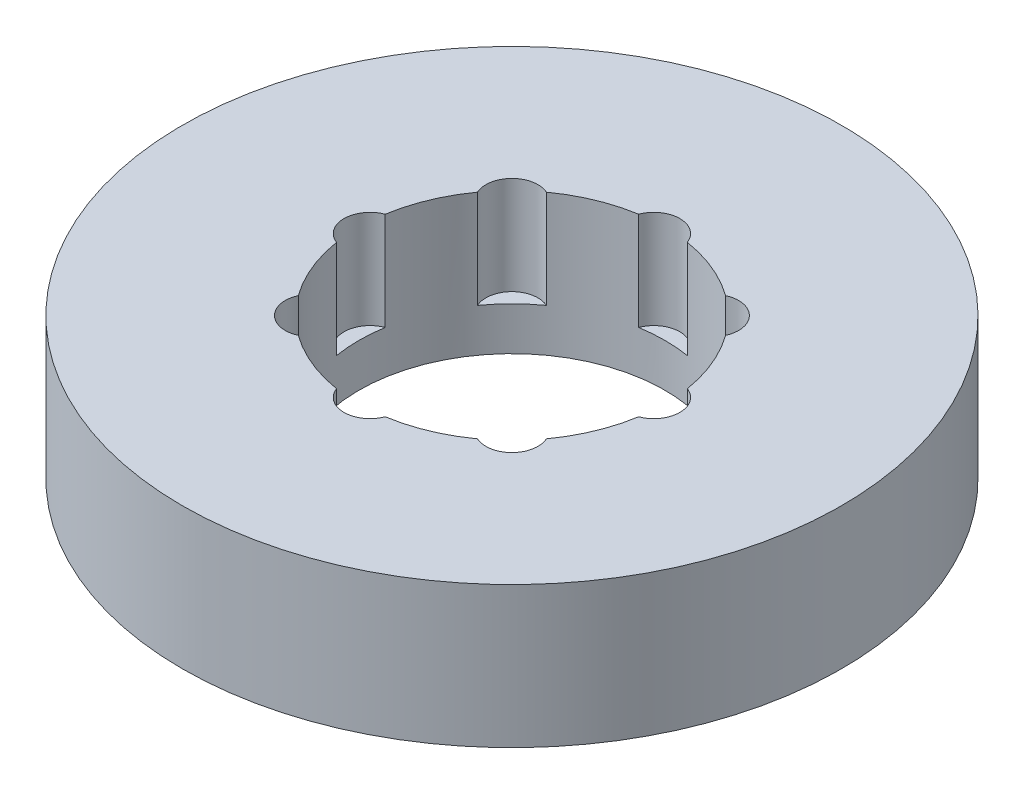
SolidWorks part; units mm, degrees
ref_plane "Front Plane" through (0, 0, 0) normal (0, 0, 1) x (1, 0, 0)
ref_plane "Top Plane" through (0, 0, 0) normal (0, 1, 0) x (1, 0, 0)
ref_plane "Right Plane" through (0, 0, 0) normal (1, 0, 0) x (0, 0, -1)
sketch "Sketch1" plane through (0, 0, 0) normal (0, 1, 0) x (1, 0, 0)
  circle A0 centre (0, 0) radius 70
  dimension "FLANGE_OD" = 140
extrude "Boss-Extrude1" add sketch "Sketch1" along normal blind 30
sketch "Sketch2" plane through (0, 0, 0) normal (0, 1, 0) x (1, 0, 0)
  circle A0 centre (0, 0) radius 32.5
  dimension "BORE_D" = 65
extrude "Cut-Extrude1" cut sketch "Sketch2" along normal through all
sketch "Sketch3" plane through (0, 30, 0) normal (0, 1, 0) x (1, 0, 0)
  circle A0 centre (0, 0) radius 30.1352 construction
  circle A1 centre (-30.1352, 0) radius 5.5294
  dimension "BOLT_D" = 11.0588
  dimension "BOLT_PCD" = 60.2703
extrude "Cut-Extrude2" cut sketch "Sketch3" against normal blind 20.8299
pattern_circular "CirPattern1" count 8 over 360 about axis through (0, 0, 0) along (0, 1, 0) of "Cut-Extrude2"
